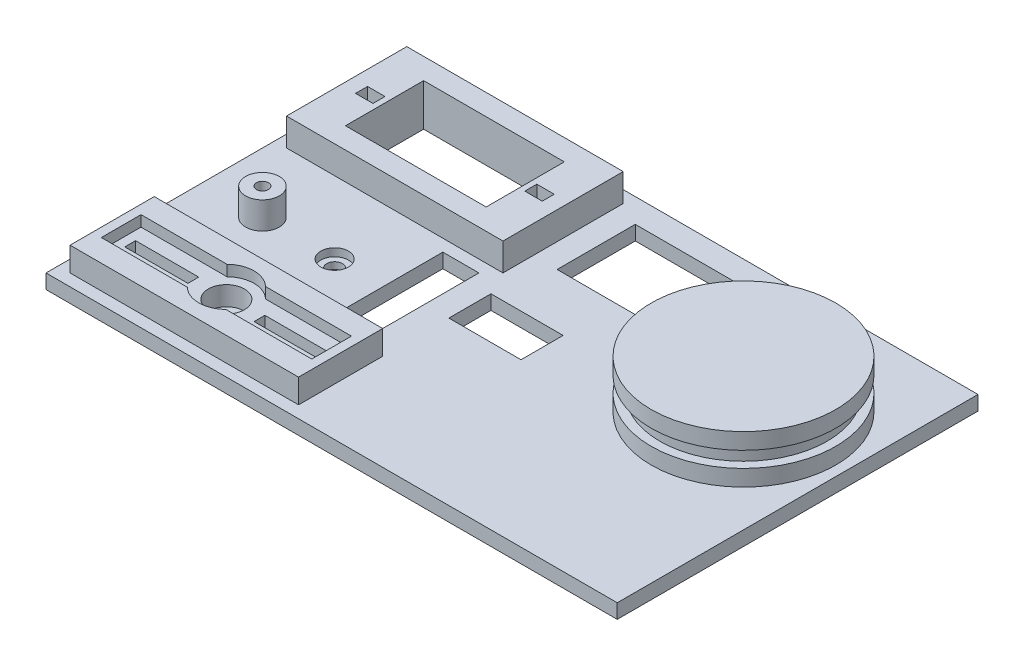
SolidWorks part; units mm, degrees
ref_plane "Front Plane" through (0, 0, 0) normal (0, 0, 1) x (1, 0, 0)
ref_plane "Top Plane" through (0, 0, 0) normal (0, 1, 0) x (1, 0, 0)
ref_plane "Right Plane" through (0, 0, 0) normal (1, 0, 0) x (0, 0, -1)
sketch "Sketch1" plane through (0, 0, 0) normal (0, 0, 1) x (1, 0, 0)
  line L1 (150, 0) -> (245, 0)
  line L2 (150, 0) -> (150, 2.4)
  line L3 (150, 2.4) -> (245, 2.4)
  line L4 (245, 0) -> (245, 2.4)
extrude "Boss-Extrude1" add sketch "Sketch1" along normal blind 60
sketch "Sketch2" plane through (0, 0, 0) normal (0, 0, 1) x (1, 0, 0)
  line L1 (152, 2.4) -> (188, 2.4)
  line L2 (152, 2.4) -> (152, 7)
  line L3 (152, 7) -> (188, 7)
  line L4 (188, 2.4) -> (188, 7)
extrude "Boss-Extrude2" add sketch "Sketch2" along normal blind 20 from offset 2
sketch "Sketch3" plane through (0, 0, 0) normal (0, 0, 1) x (1, 0, 0)
  line L1 (158.3, -1) -> (181.7, -1)
  line L2 (158.3, -1) -> (158.3, 8)
  line L3 (158.3, 8) -> (181.7, 8)
  line L4 (181.7, -1) -> (181.7, 8)
extrude "Boss-Extrude3" add sketch "Sketch3" along normal blind 13 from offset 5.5 separate body
combine bodies "Combine1" operation type subtract main body 102 bodies to subtract 103
sketch "Sketch4" plane through (0, 0, 0) normal (0, 0, 1) x (1, 0, 0)
  line L1 (154.475, -1) -> (157.375, -1)
  line L2 (154.475, -1) -> (154.475, 8)
  line L3 (154.475, 8) -> (157.375, 8)
  line L4 (157.375, -1) -> (157.375, 8)
extrude "Boss-Extrude4" add sketch "Sketch4" along normal blind 2 from offset 11 separate body
combine bodies "Combine2" operation type subtract main body 104 bodies to subtract 105
sketch "Sketch5" plane through (0, 0, 0) normal (0, 0, 1) x (1, 0, 0)
  line L1 (182.625, -1) -> (185.525, -1)
  line L2 (182.625, -1) -> (182.625, 8)
  line L3 (182.625, 8) -> (185.525, 8)
  line L4 (185.525, -1) -> (185.525, 8)
extrude "Boss-Extrude5" add sketch "Sketch5" along normal blind 2 from offset 11 separate body
combine bodies "Combine3" operation type subtract main body 106 bodies to subtract 107
sketch "Sketch6" plane through (0, 0, 0) normal (0, 0, 1) x (1, 0, 0)
  line L1 (192, -1) -> (211.4, -1)
  line L2 (192, -1) -> (192, 3.4)
  line L3 (192, 3.4) -> (211.4, 3.4)
  line L4 (211.4, -1) -> (211.4, 3.4)
extrude "Boss-Extrude6" add sketch "Sketch6" along normal blind 13 from offset 4 separate body
combine bodies "Combine4" operation type subtract main body 108 bodies to subtract 109
sketch "Sketch7" plane through (0, 0, 0) normal (0, 1, 0) x (1, 0, 0)
  circle A0 centre (160, -34) radius 2.8
extrude "Boss-Extrude7" add sketch "Sketch7" along normal blind 4.5 from offset 2.4
sketch "Sketch8" plane through (0, 0, 0) normal (0, 1, 0) x (1, 0, 0)
  circle A0 centre (160, -34) radius 1
extrude "Boss-Extrude8" add sketch "Sketch8" along normal blind 6.3 from offset 1.6 separate body
combine bodies "Combine5" operation type subtract main body 111 bodies to subtract 112
sketch "Sketch9" plane through (0, 0, 0) normal (0, 1, 0) x (1, 0, 0)
  circle A0 centre (172, -34) radius 1.3
extrude "Boss-Extrude9" add sketch "Sketch9" along normal blind 4.4 from offset 1 separate body offset against normal yes
combine bodies "Combine6" operation type subtract main body 113 bodies to subtract 114
sketch "Sketch10" plane through (0, 0, 0) normal (0, 1, 0) x (1, 0, 0)
  circle A0 centre (172, -34) radius 2.3
extrude "Boss-Extrude10" add sketch "Sketch10" along normal blind 2.3 from offset 1.1 separate body
combine bodies "Combine7" operation type subtract main body 115 bodies to subtract 116
sketch "Sketch11" plane through (0, 0, 0) normal (0, 0, 1) x (1, 0, 0)
  line L1 (180, -1) -> (186, -1)
  line L2 (180, -1) -> (180, 3.4)
  line L3 (180, 3.4) -> (186, 3.4)
  line L4 (186, -1) -> (186, 3.4)
extrude "Boss-Extrude11" add sketch "Sketch11" along normal blind 17 from offset 24 separate body
combine bodies "Combine8" operation type subtract main body 117 bodies to subtract 118
sketch "Sketch12" plane through (0, 0, 0) normal (0, 0, 1) x (1, 0, 0)
  line L1 (190, -1) -> (202, -1)
  line L2 (190, -1) -> (190, 3.4)
  line L3 (190, 3.4) -> (202, 3.4)
  line L4 (202, -1) -> (202, 3.4)
extrude "Boss-Extrude12" add sketch "Sketch12" along normal blind 7 from offset 26 separate body
combine bodies "Combine9" operation type subtract main body 119 bodies to subtract 120
sketch "Sketch13" plane through (0, 0, 0) normal (0, 1, 0) x (1, 0, 0)
  circle A0 centre (228, -22) radius 15.35
extrude "Boss-Extrude13" add sketch "Sketch13" along normal blind 8 from offset 2.4
sketch "Sketch14" plane through (0, 0, 0) normal (0, 1, 0) x (1, 0, 0)
  circle A0 centre (228, -22) radius 20
extrude "Boss-Extrude14" add sketch "Sketch14" along normal blind 2.6 from offset 5.1 separate body
combine bodies "Combine10" operation type subtract main body 122 bodies to subtract 123
sketch "Sketch15" plane through (0, 0, 0) normal (0, 1, 0) x (1, 0, 0)
  circle A0 centre (228, -22) radius 13.9
extrude "Boss-Extrude15" add sketch "Sketch15" along normal blind 2.6 from offset 5.1
sketch "Sketch16" plane through (0, 0, 0) normal (0, 0, 1) x (1, 0, 0)
  line L1 (152, 2.4) -> (190, 2.4)
  line L2 (152, 2.4) -> (152, 6.4)
  line L3 (152, 6.4) -> (190, 6.4)
  line L4 (190, 2.4) -> (190, 6.4)
extrude "Boss-Extrude16" add sketch "Sketch16" along normal blind 14 from offset 44
sketch "Sketch17" plane through (0, 0, 0) normal (0, 1, 0) x (1, 0, 0)
  circle A0 centre (171, -51) radius 4.6
extrude "Boss-Extrude17" add sketch "Sketch17" along normal blind 2.3 from offset 4.6 separate body
combine bodies "Combine11" operation type subtract main body 127 bodies to subtract 128
sketch "Sketch18" plane through (0, 0, 0) normal (0, 0, 1) x (1, 0, 0)
  line L1 (171, 4.6) -> (188.5, 4.6)
  line L2 (171, 4.6) -> (171, 6.9)
  line L3 (171, 6.9) -> (188.5, 6.9)
  line L4 (188.5, 4.6) -> (188.5, 6.9)
extrude "Boss-Extrude18" add sketch "Sketch18" along normal blind 6.6 from offset 47.7 separate body
combine bodies "Combine12" operation type subtract main body 129 bodies to subtract 130
sketch "Sketch19" plane through (0, 0, 0) normal (0, 0, 1) x (1, 0, 0)
  line L1 (176.5, 1.4) -> (187, 1.4)
  line L2 (176.5, 1.4) -> (176.5, 7.4)
  line L3 (176.5, 7.4) -> (187, 7.4)
  line L4 (187, 1.4) -> (187, 7.4)
extrude "Boss-Extrude19" add sketch "Sketch19" along normal blind 1.8 from offset 50.1 separate body
combine bodies "Combine13" operation type subtract main body 131 bodies to subtract 132
sketch "Sketch20" plane through (0, 0, 0) normal (0, 0, 1) x (1, 0, 0)
  line L1 (153.5, 4.6) -> (171, 4.6)
  line L2 (153.5, 4.6) -> (153.5, 6.9)
  line L3 (153.5, 6.9) -> (171, 6.9)
  line L4 (171, 4.6) -> (171, 6.9)
extrude "Boss-Extrude20" add sketch "Sketch20" along normal blind 6.6 from offset 47.7 separate body
combine bodies "Combine14" operation type subtract main body 133 bodies to subtract 134
sketch "Sketch21" plane through (0, 0, 0) normal (0, 0, 1) x (1, 0, 0)
  line L1 (155, 1.4) -> (165.5, 1.4)
  line L2 (155, 1.4) -> (155, 7.4)
  line L3 (155, 7.4) -> (165.5, 7.4)
  line L4 (165.5, 1.4) -> (165.5, 7.4)
extrude "Boss-Extrude21" add sketch "Sketch21" along normal blind 1.8 from offset 50.1 separate body
combine bodies "Combine15" operation type subtract main body 135 bodies to subtract 136
sketch "Sketch22" plane through (0, 0, 0) normal (0, 1, 0) x (1, 0, 0)
  circle A0 centre (171, -51) radius 3
extrude "Boss-Extrude22" add sketch "Sketch22" along normal blind 6 from offset 1.4 separate body
combine bodies "Combine16" operation type subtract main body 137 bodies to subtract 138
